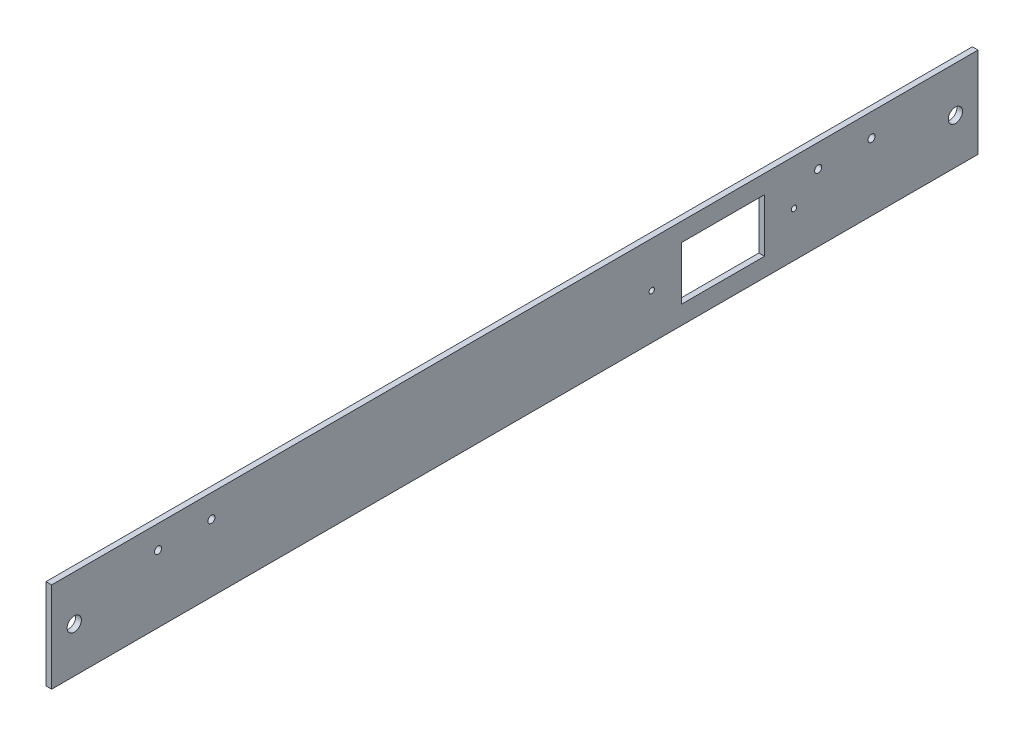
SolidWorks part; units mm, degrees
ref_plane "Front Plane" through (0, 0, 0) normal (0, 0, 1) x (1, 0, 0)
ref_plane "Top Plane" through (0, 0, 0) normal (0, 1, 0) x (1, 0, 0)
ref_plane "Right Plane" through (0, 0, 0) normal (1, 0, 0) x (0, 0, -1)
sketch "Sketch1" plane through (0, 0, 0) normal (1, 0, 0) x (0, 0, -1)
  line L1 (0, 0) -> (520.7, 0)
  line L2 (0, 0) -> (0, 50.8)
  line L3 (0, 50.8) -> (520.7, 50.8)
  line L4 (520.7, 0) -> (520.7, 50.8)
  circle A0 centre (12.7, 25.4) radius 4
  circle A1 centre (508, 25.4) radius 4
  circle A2 centre (59.825, 37.8) radius 2
  circle A3 centre (89.825, 37.8) radius 2
  circle A4 centre (430.875, 37.8) radius 2
  circle A5 centre (460.875, 37.8) radius 2
  dimension "D3" = 8
  dimension "D12" = 4
  dimension "D1" = 50.8
  dimension "D2" = 520.7
  dimension "D4" = 25.4
  dimension "D5" = 12.7
  dimension "D6" = 12.7
  dimension "D7" = 508
  dimension "D8" = 30
  dimension "D9" = 30
  dimension "D10" = 59.825
  dimension "D11" = 59.825
  dimension "D13" = 13
  dimension "D14" = 430.875
extrude "Boss-Extrude2" add sketch "Sketch1" along normal blind 3.175
sketch "ACOutletSketch2" plane through (3.175, 0, 0) normal (1, 0, 0) x (0, 0, -1)
  line L0 (520.7, 50.8) -> (0, 50.8) construction
  line L1 (353.9, 40.4) -> (400.7, 40.4)
  line L2 (353.9, 40.4) -> (353.9, 10.4)
  line L3 (353.9, 10.4) -> (400.7, 10.4)
  line L4 (400.7, 40.4) -> (400.7, 10.4)
  line L5 (520.7, 0) -> (520.7, 50.8) construction
  line L6 (0, 50.8) -> (0, 0) construction
  dimension "D1" = 46.8
  dimension "D2" = 30
  dimension "D3" = 10.4
  dimension "D4" = 120
  dimension "D5" = 353.9
  dimension "D6" = 400.7
extrude "ACOutletCut-Extrude1" cut sketch "ACOutletSketch2" against normal through all
sketch "PowerCoverMountingHolesSketch2" plane through (3.175, 0, 0) normal (1, 0, 0) x (0, 0, -1)
  line L0 (400.7, 10.4) -> (400.7, 40.4) construction
  line L1 (353.9, 40.4) -> (353.9, 10.4) construction
  line L2 (0, 50.8) -> (0, 0) construction
  circle A0 centre (337.3, 25.4) radius 1.5
  circle A1 centre (417.3, 25.4) radius 1.5
  point P8 (353.9, 25.4)
  point P12 (0, 25.4)
  dimension "D1" = 80
  dimension "D2" = 16.6
  dimension "D3" = 16.6
  dimension "D5" = 337.3
  dimension "D6" = 417.3
extrude "PowerCoverMountingHolesCut-Extrude1" cut sketch "PowerCoverMountingHolesSketch2" against normal through all
equation "\"RailThickness\"= .125in'Spec"
equation "\"VSWidth\"= 1.25in'Spec"
equation "\"LowerRailHeight\"= 2.0in"
equation "\"StepperHolePadSize\"= \"StepperHoleDiameter\""
equation "\"D1@Sketch1\"=\"LowerRailHeight\""
equation "\"D2@Sketch1\"= \"FrontOrBackRailLength\""
equation "\"FrameFastenerHoleDiameter\"= 8mm"
equation "\"D3@Sketch1\"=\"FrameFastenerHoleDiameter\""
equation "\"D4@Sketch1\"=\"LowerRailHeight\"/2"
equation "\"D5@Sketch1\"=\"FrameFastenerHoleOffsetFromEdge\""
equation "\"D6@Sketch1\"=\"FrameFastenerHoleOffsetFromEdge\""
equation "\"D1@Boss-Extrude2\"=\"RailThickness\""
equation "\"FrontOrBackRailLength\"= 20.5in"
equation "\"FrameFastenerHoleOffsetFromEdge\"= \"VSWidth\" / 2 - \"GapBetweenVerticalSupportsAndRails\" / 2"
equation "\"GapBetweenVerticalSupportsAndRails\"= \"RailThickness\" * 2"
equation "\"ACPowerOutletHeight\"= 30mm"
equation "\"D2@ACOutletSketch2\"=\"ACPowerOutletHeight\""
equation "\"ACPowerOutletWidth\"= 46.8mm"
equation "\"D1@ACOutletSketch2\"=\"ACPowerOutletWidth\""
equation "\"D3@ACOutletSketch2\"=(\"LowerRailHeight\"-\"ACPowerOutletHeight\")/2"
equation "\"AngleBracketSmallHoleDiameter\"= 4mm"
equation "\"AngleBracketSlotDistanceBetweenHoles\"= 30mm"
equation "\"AngleBracketSlotDistanceFromTop\"= 13mm"
equation "\"AngleBracketSlotDistanceFromCorner\"= \"AngleBracketSlotDistanceFromBack\" - \"GapBetweenVerticalSupportsAndRails\" / 2'Equals 61.825"
equation "\"AngleBracketSlotDistanceFromBack\"= 65mm"
equation "\"D8@Sketch1\"=\"AngleBracketSlotDistanceBetweenHoles\""
equation "\"D9@Sketch1\"=\"AngleBracketSlotDistanceBetweenHoles\""
equation "\"D10@Sketch1\"=\"AngleBracketSlotDistanceFromCorner\" -2mm"
equation "\"D11@Sketch1\"=\"AngleBracketSlotDistanceFromCorner\" -2mm"
equation "\"D12@Sketch1\"=\"AngleBracketSmallHoleDiameter\""
equation "\"D13@Sketch1\"=\"AngleBracketSlotDistanceFromTop\""
equation "\"D2@PowerCoverMountingHolesSketch2\"=( \"PowerSwitchCoverWidthBetweenMountingHoles\" - \"ACPowerOutletWidth\" )  / 2"
equation "\"PowerSwitchCoverWidth\"= 70mm"
equation "\"PowerSwitchCoverMountingTabWidth\"= 10mm"
equation "\"PowerSwitchCoverWidthBetweenMountingHoles\"= \"PowerSwitchCoverWidth\" + \"PowerSwitchCoverMountingTabWidth\""
equation "\"D1@PowerCoverMountingHolesSketch2\"=\"PowerSwitchCoverWidthBetweenMountingHoles\""
